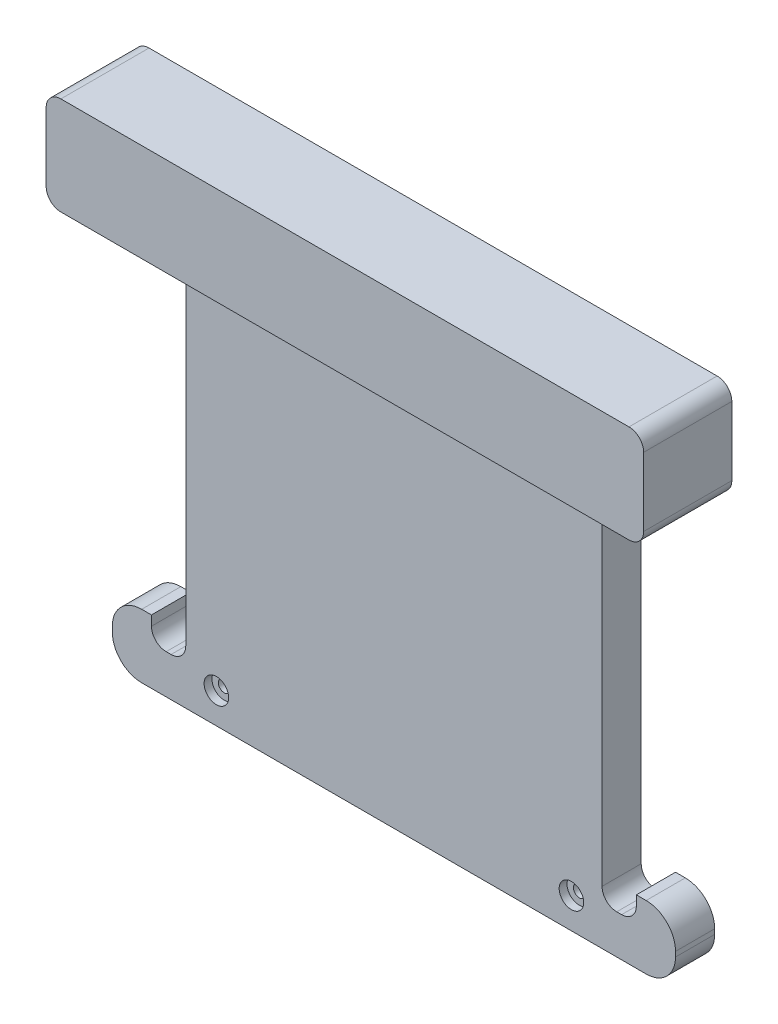
SolidWorks part; units mm, degrees
ref_plane "Front Plane" through (0, 0, 0) normal (0, 0, 1) x (1, 0, 0)
ref_plane "Top Plane" through (0, 0, 0) normal (0, 1, 0) x (1, 0, 0)
ref_plane "Right Plane" through (0, 0, 0) normal (1, 0, 0) x (0, 0, -1)
sketch "Esboço1" plane through (0, 0, 0) normal (0, 0, 1) x (1, 0, 0)
  line L0 (0, 36.25) -> (0, -36.25) construction
  line L9 (-36.25, 0) -> (36.25, 0) construction
  line L10 (-36.25, 36.25) -> (36.25, 36.25) construction
  line L11 (36.25, -36.25) -> (-36.25, -36.25) construction
  line L12 (-36.25, 36.25) -> (-36.25, -36.25) construction
  line L13 (36.25, 36.25) -> (36.25, -36.25) construction
  line L14 (0, 42.5) -> (0, -42.5) construction
  line L15 (-42.5, 42.5) -> (42.5, 42.5)
  line L16 (-42.5, 42.5) -> (-42.5, -42.5)
  line L17 (-42.5, -42.5) -> (42.5, -42.5)
  line L18 (42.5, 42.5) -> (42.5, -42.5)
  point P13 (0, 0)
  point P15 (0, 0)
  dimension "D1" = 85
  dimension "D2" = 85
extrude "Ressalto-extrusão1" add sketch "Esboço1" along normal blind 8
hole_wizard "Rebaixo para parafuso de máquina com cabeça panela de M21" positions "Esboço3" profile "Esboço4" counterbore size "M2" standard "Ansi Metric" end condition through all
sketch "Esboço3" plane through (0, 0, 8) normal (0, 0, 1) x (1, 0, 0)
  line L0 (-42.5, 42.5) -> (-42.5, -42.5) construction
  line L1 (-42.5, -42.5) -> (42.5, -42.5) construction
  line L2 (42.5, 42.5) -> (-42.5, 42.5) construction
  line L3 (0, 0) -> (0, 37.6222) construction
  point P0 (-36.25, 36.25)
  point P2 (-36.25, -36.25)
  point P16 (36.25, -36.25)
  point P17 (36.25, 36.25)
  dimension "D1" = 6.25
  dimension "D2" = 6.25
  dimension "D3" = 6.25
  dimension "D4" = 6.25
sketch "Esboço4" plane through (-36.25, 36.25, 8) normal (1, 0, 0) x (0, -1, 0)
  line L0 (0, 0) -> (0, 8)
  line L1 (0, 8) -> (1.2, 8)
  line L3 (1.2, 8) -> (1.2, 1.6)
  line L4 (1.2, 1.6) -> (2.5, 1.6)
  line L5 (2.5, 1.6) -> (2.5, 0)
  line L7 (2.5, 0) -> (0, 0)
  line L11 (0, -6.35) -> (0, 107.95) construction
  dimension "Thru Hole Dia." = 2.4
  dimension "Thru Hole Depth" = 8
  dimension "C'Bore Dia." = 5
  dimension "C'Bore Depth" = 1.6
sketch "Esboço5" plane through (0, 42.5, 0) normal (0, 1, 0) x (1, 0, 0)
  line L5 (-61, 0) -> (61, 0)
  line L6 (-61, 0) -> (-61, -8)
  line L7 (-61, -8) -> (61, -8)
  line L8 (61, 0) -> (61, -8)
  point P6 (0, 0)
  dimension "D1" = 122
  dimension "D2" = 8
extrude "Ressalto-extrusão2" add sketch "Esboço5" along normal blind 20 contours L5 L8 L7 L6
sketch "Esboço7" plane through (0, 0, 8) normal (0, 0, 1) x (1, 0, 0)
  line L1 (-61, 62.5) -> (61, 62.5)
  line L2 (-61, 62.5) -> (-61, 42.5)
  line L3 (-61, 42.5) -> (61, 42.5)
  line L4 (61, 62.5) -> (61, 42.5)
extrude "Ressalto-extrusão4" add sketch "Esboço7" along normal blind 10
sketch "Esboço8" plane through (0, 42.5, 0) normal (0, -1, 0) x (1, 0, 0)
  line L0 (0, 0) -> (0, 25.0875) construction
  line L1 (-45, 11.7) -> (-32.5, 11.7)
  line L2 (-45, 11.7) -> (-45, 8)
  line L3 (-45, 8) -> (-32.5, 8)
  line L4 (-32.5, 11.7) -> (-32.5, 8)
  line L5 (-42.5, 8) -> (42.5, 8) construction
  line L6 (-61, 0) -> (-61, 18) construction
  line L7 (45, 8) -> (32.5, 8)
  line L8 (32.5, 11.7) -> (32.5, 8)
  line L9 (45, 11.7) -> (32.5, 11.7)
  line L10 (45, 11.7) -> (45, 8)
  dimension "D1" = 12.5
  dimension "D2" = 3.7
  dimension "D3" = 16
extrude "Corte-extrusão1" cut sketch "Esboço8" against normal blind 10
sketch "Esboço10" plane through (42.5, 0, 0) normal (1, 0, 0) x (0, 0, -1)
  line L0 (-8, -42.5) -> (-8, 42.5) construction
  line L1 (-8, -34.5) -> (0, -34.5)
  line L2 (-8, -34.5) -> (-8, -42.5)
  line L3 (-8, -42.5) -> (0, -42.5)
  line L4 (0, -34.5) -> (0, -42.5)
  line L5 (0, -42.5) -> (0, 42.5) construction
  dimension "D1" = 8
extrude "Ressalto-extrusão5" add sketch "Esboço10" along normal blind 15
sketch "Esboço11" plane through (0, -34.5, 0) normal (0, 1, 0) x (1, 0, 0)
  line L1 (57.5, 0) -> (49.5, 0)
  line L2 (57.5, 0) -> (57.5, -8)
  line L3 (57.5, -8) -> (49.5, -8)
  line L4 (49.5, 0) -> (49.5, -8)
  dimension "D1" = 8
extrude "Ressalto-extrusão6" add sketch "Esboço11" along normal blind 5
fillet "Filete1" radius 6 2 edges at (57.5, -42.5, 4) (57.5, -29.5, 4)
sketch "Esboço12" plane through (-42.5, 0, 0) normal (-1, 0, 0) x (0, 0, 1)
  line L0 (0, 42.5) -> (0, -42.5) construction
  line L1 (8, -42.5) -> (0, -42.5)
  line L2 (8, -42.5) -> (8, -34.5)
  line L3 (8, -34.5) -> (0, -34.5)
  line L4 (0, -42.5) -> (0, -34.5)
  dimension "D1" = 8
extrude "Ressalto-extrusão7" add sketch "Esboço12" along normal blind 15
sketch "Esboço13" plane through (0, -34.5, 0) normal (0, 1, 0) x (1, 0, 0)
  line L0 (-57.5, -8) -> (-42.5, -8) construction
  line L1 (-57.5, 0) -> (-49.5, 0)
  line L2 (-57.5, 0) -> (-57.5, -8)
  line L3 (-57.5, -8) -> (-49.5, -8)
  line L4 (-49.5, 0) -> (-49.5, -8)
  dimension "D1" = 8
extrude "Ressalto-extrusão8" add sketch "Esboço13" along normal blind 5
fillet "Filete2" radius 6 2 edges at (-57.5, -29.5, 4) (-57.5, -42.5, 4)
fillet "Filete3" radius 3 2 edges at (-49.5, -34.5, 4) (-42.5, -34.5, 4)
fillet "Filete4" radius 3 2 edges at (42.5, -34.5, 4) (49.5, -34.5, 4)
fillet "Filete5" radius 6 2 edges at (-42.5, 42.5, 4) (42.5, 42.5, 4)
fillet "Filete6" radius 3 4 edges at (61, 62.5, 9) (61, 42.5, 9) (-61, 62.5, 9) (-61, 42.5, 9)
